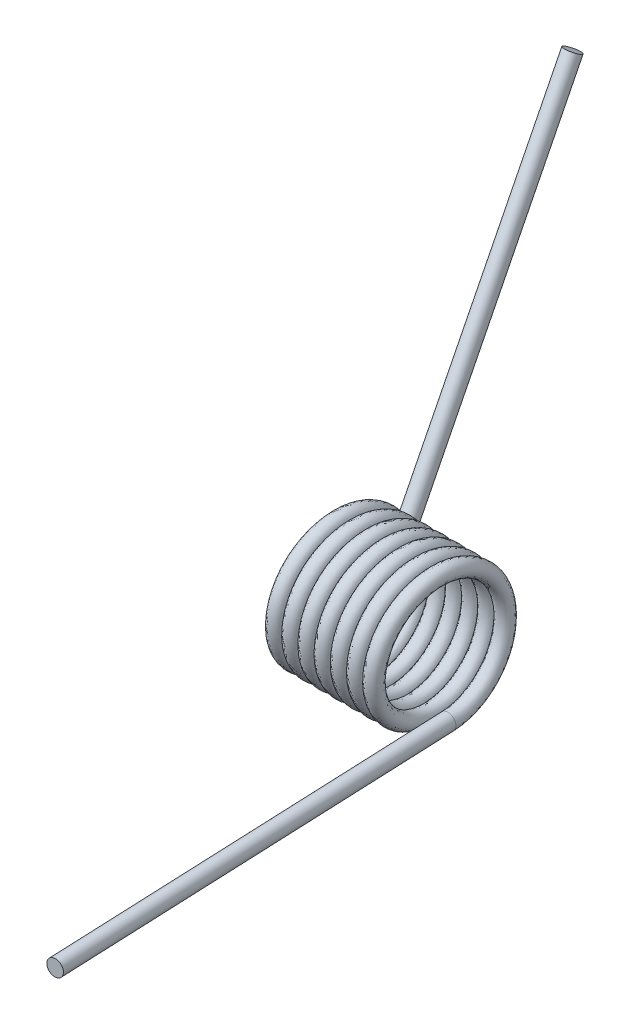
SolidWorks part; units mm, degrees
ref_plane "Front" through (0, 0, 0) normal (0, 0, 1) x (1, 0, 0)
ref_plane "Top" through (0, 0, 0) normal (0, 1, 0) x (1, 0, 0)
ref_plane "Right" through (0, 0, 0) normal (1, 0, 0) x (0, 0, -1)
sketch "Sketch1" plane through (0, 0, 0) normal (1, 0, 0) x (0, 0, -1)
  line L0 (0, 0) -> (0, -6.6294) construction
  line L1 (0, -6.6294) -> (0, -7.62) construction
  line L2 (0, -7.62) -> (0, -8.6106) construction
  line L3 (0, 8.6106) -> (0, -8.6106) construction
  circle A0 centre (0, 0) radius 6.6294 construction
  circle A1 centre (0, 0) radius 8.6106 construction
  circle A2 centre (0, 0) radius 7.62
  circle A3 centre (0, -7.62) radius 0.9906 construction
  circle A4 centre (0, 0) radius 5.1562 construction
  dimension "Wire Dia" = 1.9812
  dimension "Spring OD" = 17.2212
  dimension "Max Rod OD" = 10.3124
curve "Helix/Spiral1" pitch 2.0066 height 14.3806 radius 7.62 left hand yes centre (0, 0, 0) axis (-1, 0, 0) start towards (0, 0, -1)
ref_plane "Plane1" through (0, -7.62, 0) normal (-0.0419, 0, -0.9991) x (0.9988, -0.024, -0.0419)
sketch "Sketch2" plane through (0, -7.62, 0) normal (-0.0419, 0, -0.9991) x (0.9988, -0.024, -0.0419)
  circle A0 centre (0, 0) radius 0.9906
  dimension "D1" = 1.9812
sweep "Sweep1" add profiles "Sketch2" path "Helix/Spiral1"
sketch "Sketch3" plane through (0, 0, 0) normal (0.0419, 0, 0.9991) x (-0.9988, 0.024, 0.0419)
  circle A1 centre (-0.1826, 7.6178) radius 0.9906
  circle A2 centre (-0.1826, 7.6178) radius 0.9906
  dimension "D1" = 0
extrude "Extrude1" add sketch "Sketch3" along normal blind 50.8
sketch "Sketch4" plane through (-0.0252, 0.521, -0.3008) normal (-0.0419, 0.8653, -0.4996) x (0.9991, 0.0363, -0.0209)
  circle A1 centre (-14.368, 7.62) radius 0.9906
  circle A2 centre (-14.368, 7.62) radius 0.9906
  dimension "D1" = 0
extrude "Extrude2" add sketch "Sketch4" along normal blind 50.8
ref_plane "Plane2" through (-0.0252, 0.521, -0.3008) normal (0.0419, -0.8653, 0.4996) x (0.9991, 0.0363, -0.0209)
ref_plane "Plane3" through (0, 0, 0) normal (0.0419, 0, 0.9991) x (0.9991, 0, -0.0419)
ref_axis "Axis1" through (-298.6411, -6.5303, 12.5163) along (0.9988, 0.0242, -0.0419)
equation "\"D4@Helix/Spiral1\"=\"Wire Dia@Sketch1\"+.001"
equation "\"D1@Sketch2\"=\"Wire Dia@Sketch1\""
